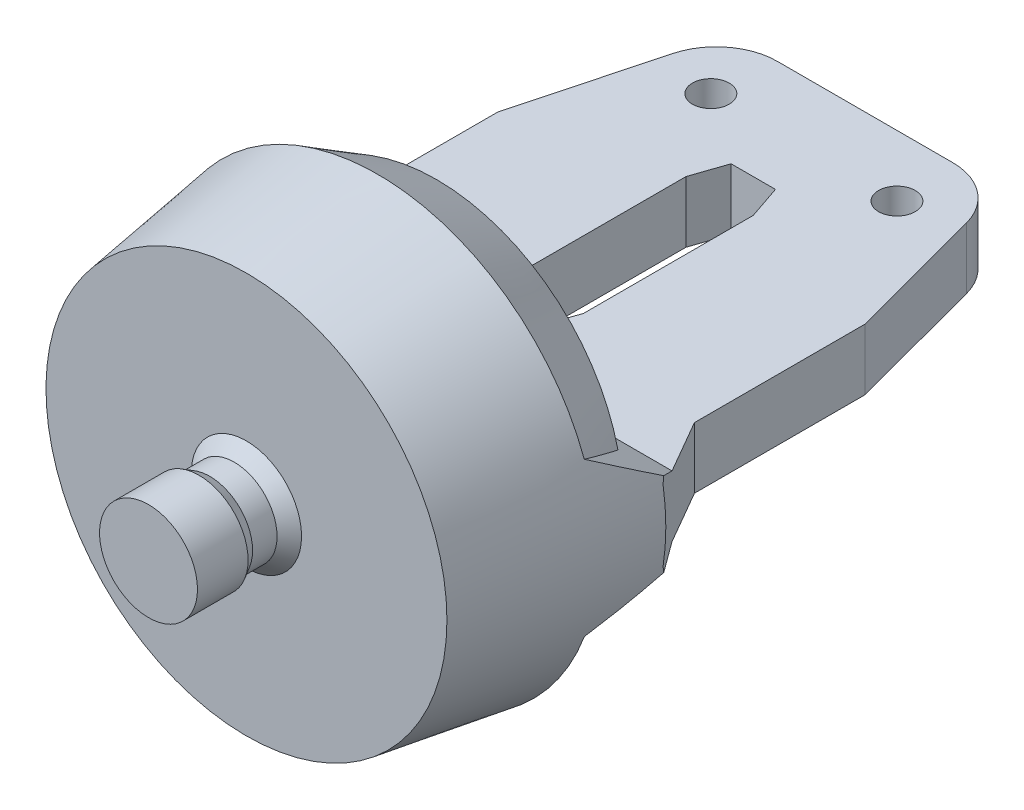
SolidWorks part; units mm, degrees
ref_plane "Przednia" through (0, 0, 0) normal (0, 0, 1) x (1, 0, 0)
ref_plane "Górna" through (0, 0, 0) normal (0, 1, 0) x (1, 0, 0)
ref_plane "Prawa" through (0, 0, 0) normal (1, 0, 0) x (0, 0, -1)
sketch "Szkic1" plane through (0, 0, 0) normal (0, 0, 1) x (1, 0, 0)
  circle A0 centre (0, 0) radius 9.5
  dimension "D1" = 19
extrude "Dodanie-wyciągnięcie1" add sketch "Szkic1" along normal blind 14
chamfer "Sfazowanie1" distance 1.5 angle 45 1 edges at (9.5, 0, 14)
ref_plane "Płaszczyzna1" through (0, 0, 7) normal (0, 0, 1) x (1, 0, 0)
sketch "Szkic2" plane through (0, 0, 7) normal (0, 0, 1) x (1, 0, 0)
  line L0 (0, 0) -> (14.476, 0) construction
  line L1 (9.2297, 2.25) -> (11.7297, 2.25)
  line L2 (12.2297, 1.75) -> (12.2297, -1.75)
  line L3 (9.2297, -2.25) -> (11.7297, -2.25)
  circle A0 centre (0, 0) radius 9.5 construction
  arc A1 (9.2297, 2.25) -> (9.2297, -2.25) centre (0, 0) cw
  arc A2 (11.7297, -2.25) -> (12.2297, -1.75) centre (11.7297, -1.75) ccw
  arc A3 (11.7297, 2.25) -> (12.2297, 1.75) centre (11.7297, 1.75) cw
  point P11 (12.2297, 0)
  point P13 (12.2297, -2.25)
  point P16 (12.2297, 2.25)
  dimension "D3" = 0.5
  dimension "D1" = 4.5
  dimension "D2" = 3
extrude "Dodanie-wyciągnięcie2" add sketch "Szkic2" along normal blind 2.9
mirror "Lustro1" about plane through (0, 0, 0) normal (1, 0, 0) of "Dodanie-wyciągnięcie2"
sketch "Szkic3" plane through (0, 0, 0) normal (0, 0, -1) x (-1, 0, 0)
  circle A0 centre (0, 0) radius 16.375
  dimension "D1" = 32.75
extrude "Dodanie-wyciągnięcie3" add sketch "Szkic3" along normal blind 3
sketch "Szkic4" plane through (0, 0, 0) normal (0, 1, 0) x (1, 0, 0)
  line L0 (0, 0) -> (0, 82.4335) construction
  line L1 (16.375, 3) -> (18.7246, 18.5286)
  line L2 (18.7246, 18.5286) -> (0, 18.5286)
  line L3 (0, 18.5286) -> (0, 3)
  line L4 (16.375, 3) -> (-16.375, 3) construction
  line L5 (0, 3) -> (16.375, 3)
revolve "Obrót1" add sketch "Szkic4" angle 360 about L0
sketch "Szkic5" plane through (0, 0, 0) normal (0, 1, 0) x (1, 0, 0)
  line L0 (0, 0) -> (0, 81.0613) construction
  line L1 (-9.5, 0) -> (9.5, 0) construction
  line L2 (18.7246, 18.5286) -> (-18.7246, 18.5286) construction
  line L3 (15, 18.5286) -> (-15, 18.5286)
  line L4 (15, 18.5286) -> (15, 53.5286)
  line L5 (15, 53.5286) -> (-15, 53.5286)
  line L6 (-15, 18.5286) -> (-15, 53.5286)
  dimension "D1" = 30
  dimension "D2" = 35
extrude "Dodanie-wyciągnięcie4" add sketch "Szkic5" along normal mid plane 5
ref_axis "Oś1" through (0, 0, 12.5) along (0, 0, -1)
sketch "Szkic7" plane through (0, 2.5, 0) normal (0, 1, 0) x (1, 0, 0)
  line L0 (0, 53.5286) -> (0, 18.5286) construction
  line L1 (15, 53.5286) -> (-15, 53.5286) construction
  line L2 (18.7246, 18.5286) -> (-18.7246, 18.5286) construction
  line L3 (-15, 18.5286) -> (15, 18.5286) construction
  circle A0 centre (7.6, 48.5286) radius 1.5
  circle A1 centre (-7.6, 48.5286) radius 1.5
  dimension "D1" = 3
  dimension "D2" = 15.2
  dimension "D3" = 30
extrude "Wytnij-wyciągnięcie1" cut sketch "Szkic7" against normal blind 10
chamfer "Sfazowanie2" distance 4 distance2 15 1 edges at (-15, 0, -53.5286) first distance on face at (0, 0, -53.5286)
chamfer "Sfazowanie3" distance 15 distance2 4 1 edges at (15, 0, -53.5286) first distance on face at (15, 0, -36.0286)
fillet "Zaokrąglenie2" radius 5 2 edges at (11, 0, -53.5286) (-11, 0, -53.5286)
sketch "Szkic8" plane through (0, 2.5, 0) normal (0, 1, 0) x (1, 0, 0)
  line L0 (0, 41.646) -> (0, 27.7866) construction
  line L1 (0, -12.5) -> (0, 29.7372) construction
  line L2 (2.7477, 41.646) -> (2.7477, 27.7866)
  line L3 (-2.7477, 41.646) -> (-2.7477, 27.7866)
  line L4 (-1.8124, 44.3938) -> (1.8124, 44.3938)
  line L5 (1.8124, 44.3938) -> (2.7477, 41.646)
  line L6 (0, 41.646) -> (0, 46.0813) construction
  line L7 (-1.8124, 44.3938) -> (-2.7477, 41.646)
  line L8 (0, 34.7163) -> (8.8559, 34.7163) construction
  line L9 (-1.8124, 25.0389) -> (-2.7477, 27.7866)
  line L10 (-1.8124, 25.0389) -> (1.8124, 25.0389)
  line L11 (1.8124, 25.0389) -> (2.7477, 27.7866)
  point P5 (0, 34.7163)
  point P16 (0, 44.3938)
extrude "Wytnij-wyciągnięcie2" cut sketch "Szkic8" against normal through all
ref_plane "Płaszczyzna2" through (0, 0, -3) normal (0, 0, 1) x (1, 0, 0)
chamfer "Sfazowanie9" distance 3.5 angle 60 2 edges at (-15, 0, -18.5286) (15, 0, -18.5286) first distance on face at (0, 0, -18.5286)
chamfer "Sfazowanie10" distance 1 angle 60 2 edges at (0, -2.5, -18.5286) (0, 2.5, -18.5286) first distance on face at (0, 0, -18.5286)
chamfer "Sfazowanie11" distance 3.5 angle 60 2 edges at (0, 18.7246, -18.5286) (0, -18.7246, -18.5286) first distance on face at (0, 11.1123, -18.5286) first distance on face at (0, -11.1123, -18.5286)
sketch "Szkic9" plane through (0, 0, -3) normal (0, 0, 1) x (1, 0, 0)
  circle A0 centre (0, 0) radius 30.7177
extrude "Wytnij-wyciągnięcie3" cut sketch "Szkic9" along normal through all
sketch "Szkic10" plane through (0, 0, -3) normal (0, 0, 1) x (1, 0, 0)
  circle A0 centre (0, 0) radius 4.05
  dimension "D1" = 8.1
extrude "Wytnij-wyciągnięcie4" [suppressed] cut sketch "Szkic10" against normal blind 10
chamfer "Sfazowanie4" [suppressed] distance 1.5 angle 45
sketch "Szkic11" plane through (0, 0, -3) normal (0, 0, 1) x (1, 0, 0)
  circle A0 centre (0, 0) radius 4
  dimension "D1" = 8
extrude "Dodanie-wyciągnięcie5" add sketch "Szkic11" along normal blind 8
sketch "Szkic12" plane through (0, 0, -3) normal (0, 0, 1) x (1, 0, 0)
  circle A0 centre (0, 0) radius 4.4452
  circle A1 centre (0, 0) radius 3.5
  circle A2 centre (0, 0) radius 4 construction
  dimension "D1" = 0.5
extrude "Wytnij-wyciągnięcie5" cut sketch "Szkic12" along normal blind 4
chamfer "Sfazowanie5" distance 1 angle 30 1 edges at (3.5, 0, 1) first distance on face at (3.5, 0, 1)
chamfer "Sfazowanie6" distance 1 angle 45 1 edges at (3.5, 0, -3)
